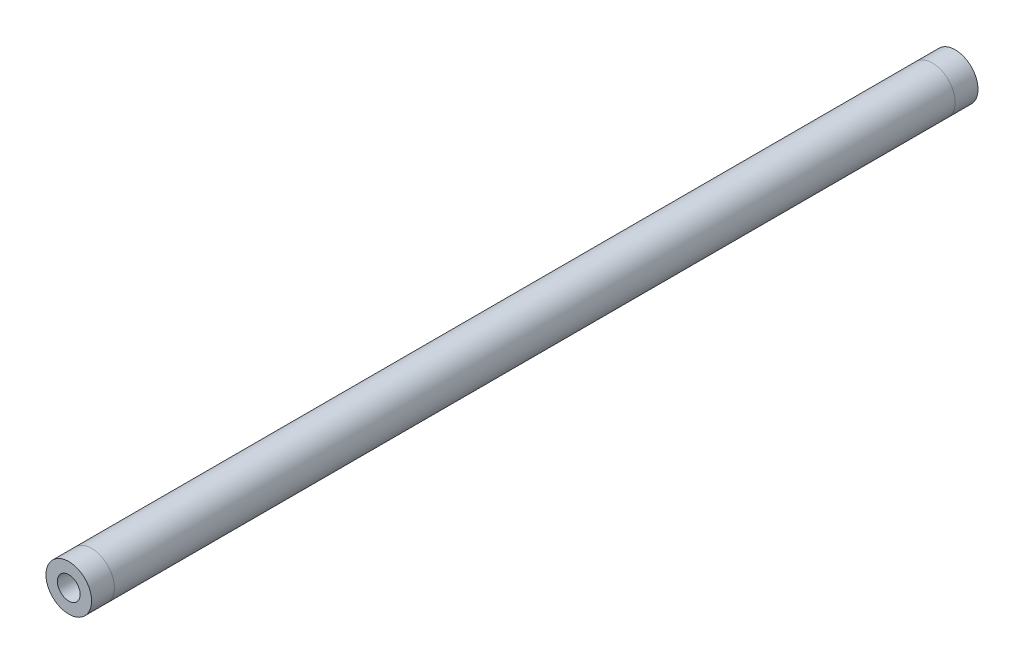
SolidWorks part; units mm, degrees
material "AISI 4130 Steel, normalized at 870C"
ref_plane "Front Plane" through (0, 0, 0) normal (0, 0, 1) x (1, 0, 0)
ref_plane "Top Plane" through (0, 0, 0) normal (0, 1, 0) x (1, 0, 0)
ref_plane "Right Plane" through (0, 0, 0) normal (1, 0, 0) x (0, 0, -1)
sketch "Axis" plane through (0, 0, 0) normal (1, 0, 0) x (0, 0, -1)
  line L0 (0, 0) -> (246.7503, 0) construction
  line L1 (246.7503, 0) -> (240.4003, 0)
  line L2 (246.7503, 0) -> (268.6451, 0) construction
  line L3 (0, 0) -> (-21.8948, 0) construction
  line L4 (-21.8948, 0) -> (-95.3875, 0)
  point P4 (0, 0)
  point P5 (246.7503, 0)
  point P6 (240.4003, 0)
  dimension "D1" = 6.35
  dimension "D2" = 21.8948
  dimension "D3" = 21.8948
sketch "Sketch1" plane through (0, 0, 0) normal (0, 0, 1) x (1, 0, 0)
  circle A0 centre (0, 0) radius 6.35
  circle A1 centre (0, 0) radius 4.8768
  circle A2 centre (0, 0) radius 3.175
  dimension "D1" = 12.7
  dimension "D2" = 1.4732
  dimension "D3" = 6.35
extrude "Threaded insert 1-1" add sketch "Sketch1" against normal blind 6.35 contours A0 A1 | A1 A2 region at (-6.1704, 0, 0) region at (-4.7389, 0, 0)
extrude "Threaded insert 1-2" add sketch "Sketch1<3>" against normal blind 9.525 from surface contours A1 A2 region at (-4.7389, 0, 0) starting at face at (6.35, 0, -6.35)
sketch "Sketch1<3>" plane through (0, 0, 0) normal (0, 0, 1) x (1, 0, 0) same geometry as "Sketch1"
extrude "Tube extrude" add sketch "Sketch1<4>" against normal up to vertex (240.4003 mm away) from surface separate body contours A0 A1 region at (-6.1704, 0, 0) up to point (0, 0, -240.4003) starting at face at (4.8768, 0, -6.35)
sketch "Sketch1<4>" plane through (0, 0, 0) normal (0, 0, 1) x (1, 0, 0) same geometry as "Sketch1"
extrude "Threaded insert 2-1" add sketch "Sketch1<6>" along normal blind 9.525 from surface separate body contours A1 A2 region at (-4.7389, 0, 0) starting at face at (4.8768, 0, -240.4003)
sketch "Sketch1<6>" plane through (0, 0, 0) normal (0, 0, 1) x (1, 0, 0) same geometry as "Sketch1"
extrude "Threaded insert 2-2" add sketch "Sketch1<9>" against normal blind 6.35 from surface separate body contours A1 A2 | A0 A1 region at (-6.1704, 0, 0) region at (-4.7389, 0, 0) starting at face at (4.8768, 0, -240.4003)
sketch "Sketch1<9>" plane through (0, 0, 0) normal (0, 0, 1) x (1, 0, 0) same geometry as "Sketch1"
combine bodies "Combine1" operation type add bodies to combine 106 104
equation "\"Threaded insert outer thickness\"= .25"
equation "\"D1@Threaded insert 1-1\"=\"Threaded insert outer thickness\""
equation "\"D1@Threaded insert 2-2\"=\"Threaded insert outer thickness\""
equation "\"D1@Axis\" = \"Threaded insert outer thickness\""
